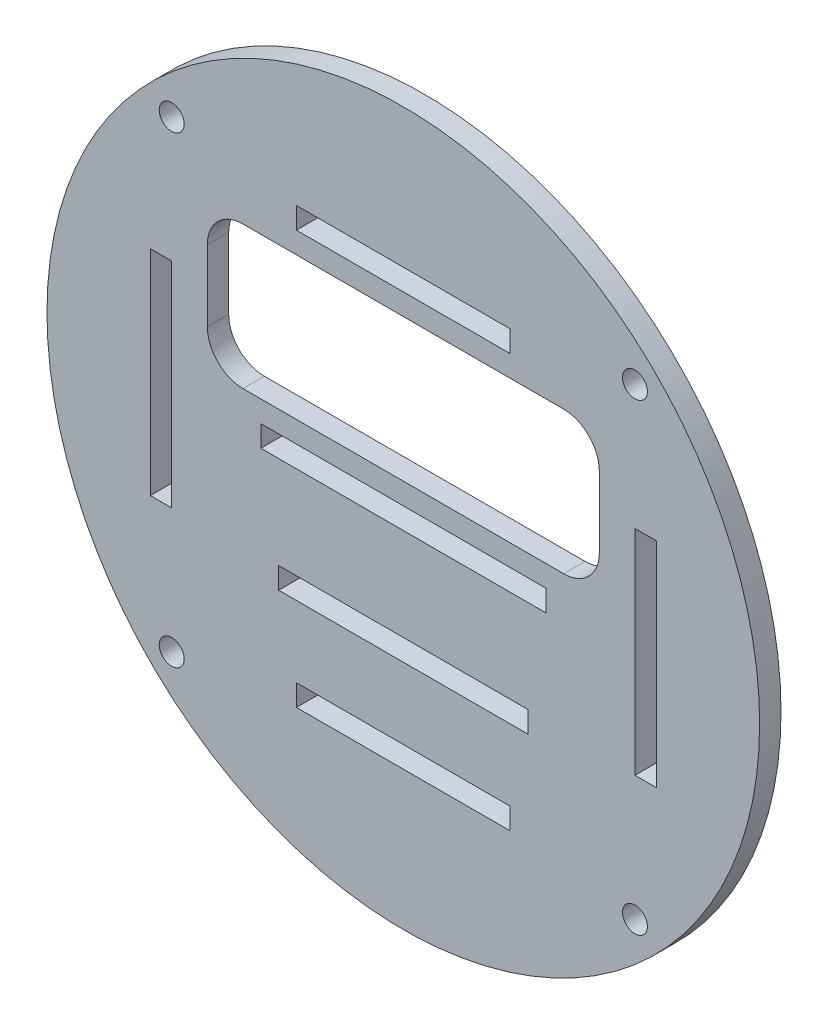
SolidWorks part; units mm, degrees
material "ABS"
ref_plane "Спереди" through (0, 0, 0) normal (0, 0, 1) x (1, 0, 0)
ref_plane "Сверху" through (0, 0, 0) normal (0, 1, 0) x (1, 0, 0)
ref_plane "Справа" through (0, 0, 0) normal (1, 0, 0) x (0, 0, -1)
sketch "Эскиз1" plane through (0, 0, 0) normal (0, 0, 1) x (1, 0, 0)
  circle A0 centre (0, 0) radius 50
  dimension "D1" = 100
extrude "Бобышка-Вытянуть1" add sketch "Эскиз1" along normal blind 3
sketch "Эскиз2" plane through (0, 0, 3) normal (0, 0, 1) x (1, 0, 0)
  line L0 (0, 50) -> (0, -50) construction
  line L1 (-50, 0) -> (50, 0) construction
  line L2 (-15, -27.5) -> (15, -27.5)
  line L3 (-15, -27.5) -> (-15, -30.5)
  line L4 (-15, -30.5) -> (15, -30.5)
  line L5 (15, -27.5) -> (15, -30.5)
  line L6 (-15, -27.5) -> (15, -30.5) construction
  line L7 (-15, -30.5) -> (15, -27.5) construction
  line L8 (-17.5, -14.5) -> (17.5, -14.5)
  line L9 (-17.5, -14.5) -> (-17.5, -17.5)
  line L10 (-17.5, -17.5) -> (17.5, -17.5)
  line L11 (17.5, -14.5) -> (17.5, -17.5)
  line L12 (-17.5, -14.5) -> (17.5, -17.5) construction
  line L13 (-17.5, -17.5) -> (17.5, -14.5) construction
  line L14 (-20, 1.5) -> (20, 1.5)
  line L15 (-20, 1.5) -> (-20, -1.5)
  line L16 (-20, -1.5) -> (20, -1.5)
  line L17 (20, 1.5) -> (20, -1.5)
  line L18 (-20, 1.5) -> (20, -1.5) construction
  line L19 (-20, -1.5) -> (20, 1.5) construction
  line L20 (-15, 30.5) -> (15, 27.5) construction
  line L21 (-15, 27.5) -> (15, 30.5) construction
  line L22 (15, 27.5) -> (15, 30.5)
  line L23 (-15, 30.5) -> (15, 30.5)
  line L24 (-15, 27.5) -> (-15, 30.5)
  line L25 (-15, 27.5) -> (15, 27.5)
  circle A0 centre (0, 0) radius 50 construction
  point P5 (0, -29)
  point P10 (0, -16)
  point P16 (0, 0)
  point P27 (0, 29)
  dimension "D1" = 3
  dimension "D2" = 30
  dimension "D3" = 27.5
  dimension "D4" = 3
  dimension "D5" = 35
  dimension "D6" = 10
  dimension "D7" = 3
  dimension "D8" = 40
extrude "Вырез-Вытянуть1" cut sketch "Эскиз2" against normal blind 8
sketch "Эскиз3" plane through (0, 0, 0) normal (0, 0, -1) x (-1, 0, 0)
  line L0 (-20, 1.5) -> (20, 1.5) construction
  line L1 (-22.5, 24.5) -> (22.5, 24.5)
  line L2 (-27.5, 19.5) -> (-27.5, 9.5)
  line L3 (-22.5, 4.5) -> (22.5, 4.5)
  line L4 (27.5, 19.5) -> (27.5, 9.5)
  line L5 (-27.5, 24.5) -> (27.5, 4.5) construction
  line L6 (-27.5, 4.5) -> (27.5, 24.5) construction
  line L7 (0, 0) -> (0, 36.6116) construction
  arc A0 (-27.5, 9.5) -> (-22.5, 4.5) centre (-22.5, 9.5) ccw
  arc A1 (22.5, 4.5) -> (27.5, 9.5) centre (22.5, 9.5) ccw
  arc A2 (22.5, 24.5) -> (27.5, 19.5) centre (22.5, 19.5) cw
  arc A3 (-22.5, 24.5) -> (-27.5, 19.5) centre (-22.5, 19.5) ccw
  point P0 (0, 14.5)
  point P10 (0, 0)
  dimension "D4" = 5
  dimension "D1" = 3
  dimension "D2" = 20
  dimension "D3" = 55
extrude "Вырез-Вытянуть2" cut sketch "Эскиз3" against normal blind 10
sketch "Эскиз4" plane through (0, 0, 0) normal (0, 0, -1) x (-1, 0, 0)
  line L0 (0, 50) -> (0, -50) construction
  line L1 (-50, 0) -> (50, 0) construction
  line L2 (32.5, -15) -> (35.4957, 15) construction
  line L3 (-32.5, 15) -> (-35.4957, 15)
  line L4 (-32.5, 15) -> (-32.5, -15)
  line L5 (-32.5, -15) -> (-35.4957, -15)
  line L6 (-35.4957, 15) -> (-35.4957, -15)
  line L7 (-32.5, 15) -> (-35.4957, -15) construction
  line L8 (-32.5, -15) -> (-35.4957, 15) construction
  line L9 (32.5, 15) -> (35.4957, -15) construction
  line L10 (35.4957, 15) -> (35.4957, -15)
  line L11 (32.5, -15) -> (35.4957, -15)
  line L12 (32.5, 15) -> (32.5, -15)
  line L13 (32.5, 15) -> (35.4957, 15)
  circle A0 centre (0, 0) radius 50 construction
  point P7 (-33.9978, 0)
  point P17 (33.9978, 0)
  dimension "D1" = 2.9957
  dimension "D2" = 30
  dimension "D3" = 32.5
extrude "Вырез-Вытянуть3" cut sketch "Эскиз4" against normal blind 10
sketch "Эскиз5" plane through (0, 0, 3) normal (0, 0, 1) x (1, 0, 0)
  line L1 (-32.5, -32.5) -> (32.5, -32.5) construction
  line L2 (-32.5, -32.5) -> (-32.5, 32.5) construction
  line L3 (-32.5, 32.5) -> (32.5, 32.5) construction
  line L4 (32.5, -32.5) -> (32.5, 32.5) construction
  line L5 (-32.5, -32.5) -> (32.5, 32.5) construction
  line L6 (-32.5, 32.5) -> (32.5, -32.5) construction
  circle A0 centre (-32.5, 32.5) radius 1.75
  circle A1 centre (32.5, 32.5) radius 1.75
  circle A2 centre (32.5, -32.5) radius 1.75
  circle A3 centre (-32.5, -32.5) radius 1.75
  point P0 (0, 0)
  dimension "D3" = 3.5
  dimension "D1" = 65
  dimension "D2" = 65
extrude "Вырез-Вытянуть4" cut sketch "Эскиз5" against normal blind 10
